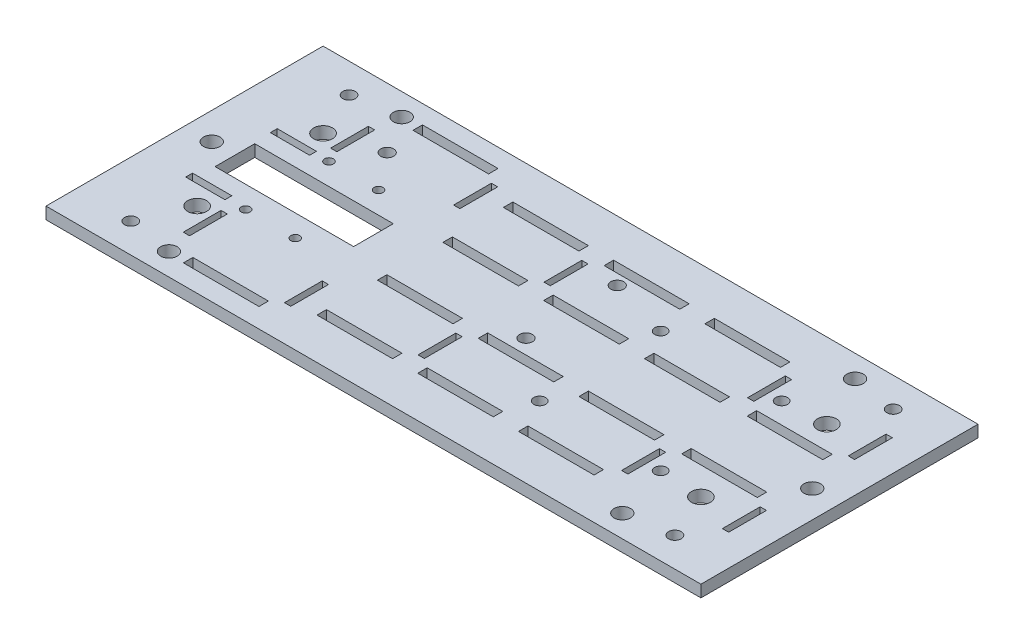
SolidWorks part; units mm, degrees
material "Thornel VCB-20 Carbon Cloth"
ref_plane "Front Plane" through (0, 0, 0) normal (0, 0, 1) x (1, 0, 0)
ref_plane "Top Plane" through (0, 0, 0) normal (0, 1, 0) x (1, 0, 0)
ref_plane "Right Plane" through (0, 0, 0) normal (1, 0, 0) x (0, 0, -1)
sketch "Sketch1" plane through (0, 0, 0) normal (0, 1, 0) x (1, 0, 0)
  line L0 (82.55, -34.925) -> (82.55, 34.925)
  line L1 (82.55, -34.925) -> (-82.55, -34.925)
  line L2 (82.55, 34.925) -> (-82.55, 34.925)
  line L3 (-82.55, -34.925) -> (-82.55, 34.925)
  line L4 (82.55, -34.925) -> (-82.55, 34.925) construction
  line L5 (82.55, 34.925) -> (-82.55, -34.925) construction
  point P1 (0, 0)
  dimension "D1" = 165.1
  dimension "D2" = 69.85
extrude "Boss-Extrude1" add sketch "Sketch1" along normal blind 3
sketch "Sketch6" plane through (0, 0, 0) normal (0, -1, 0) x (1, 0, 0)
  line L0 (-82.55, -34.925) -> (-82.55, 34.925) construction
  line L1 (-69.85, 5) -> (-34.925, 5)
  line L2 (-69.85, 5) -> (-69.85, -5)
  line L3 (-69.85, -5) -> (-34.925, -5)
  line L4 (-34.925, 5) -> (-34.925, -5)
  line L5 (6.775, -19.756) -> (-51.225, -19.756) construction
  line L6 (6.775, -19.756) -> (6.775, 3.246) construction
  line L7 (6.775, 3.246) -> (-51.225, 3.246) construction
  line L8 (-51.225, -19.756) -> (-51.225, 3.246) construction
  line L9 (6.775, -19.756) -> (-51.225, 3.246) construction
  line L10 (6.775, 3.246) -> (-51.225, -19.756) construction
  circle A0 centre (22.225, 15.25) radius 1.5
  circle A1 centre (52.725, 15.25) radius 1.5
  circle A2 centre (22.225, -15.25) radius 1.5
  circle A3 centre (52.725, -15.25) radius 1.5
  circle A4 centre (-51.225, 3.246) radius 1.625
  circle A5 centre (6.775, 3.246) radius 1.625
  circle A6 centre (6.775, -19.756) radius 1.625
  circle A7 centre (-51.225, -19.756) radius 1.625
  point P8 (-34.925, 0)
  point P9 (0, 0)
  point P16 (34.8354, 15.25)
  point P18 (-22.225, -8.255)
  point P27 (-26.6476, 0)
  point P28 (-25.4, -11.677)
  point P29 (-31.75, -5.9882)
  dimension "D5" = 3
  dimension "D6" = 3
  dimension "D7" = 3
  dimension "D8" = 3
  dimension "D18" = 3.25
  dimension "D1" = 34.925
  dimension "D2" = 10
  dimension "D3" = 12.7
  dimension "D4" = 30.5
  dimension "D9" = 30.5
  dimension "D10" = 30.5
  dimension "D11" = 15.25
  dimension "D12" = 22.225
  dimension "D13" = 15.25
  dimension "D14" = 15.25
  dimension "D15" = 15.25
  dimension "D16" = 23.002
  dimension "D17" = 58
  dimension "D19" = 60.325
  dimension "D20" = 8.255
extrude "Cut-Extrude1" cut sketch "Sketch6" against normal up to next contours A4 | L4 L1 L2 L3 A4 | A6 | A2 | A3 | A1 | A0 | A7 | A5 region at (-52.4158, 0, -0.079) region at (22.225, 0, 15.25) region at (52.725, 0, 15.25) region at (22.225, 0, -15.25) region at (52.725, 0, -15.25) region at (-51.225, 0, 3.246) region at (6.775, 0, -19.756)
sketch "Sketch7" plane through (0, 3, 0) normal (0, 1, 0) x (1, 0, 0)
  line L0 (-82.55, 34.925) -> (-82.55, -34.925) construction
  line L1 (82.55, -34.925) -> (82.55, 34.925) construction
  line L2 (-82.55, -34.925) -> (82.55, -34.925) construction
  line L3 (82.55, 34.925) -> (-82.55, 34.925) construction
  circle A0 centre (-77.47, 29.845) radius 1.5
  circle A1 centre (-77.47, -29.845) radius 1.5
  circle A2 centre (77.47, -29.845) radius 1.5
  circle A3 centre (77.47, 29.845) radius 1.5
  dimension "D9" = 3
  dimension "D10" = 3
  dimension "D11" = 3
  dimension "D12" = 3
  dimension "D1" = 5.08
  dimension "D2" = 5.08
  dimension "D3" = 5.08
  dimension "D4" = 5.08
  dimension "D5" = 5.08
  dimension "D6" = 5.08
  dimension "D7" = 5.08
  dimension "D8" = 5.08
sketch "Sketch8" plane through (0, 3, 0) normal (0, 1, 0) x (1, 0, 0)
  line L0 (-82.55, -34.925) -> (82.55, -34.925) construction
  line L1 (-82.55, 34.925) -> (-82.55, -34.925) construction
  line L2 (82.55, -34.925) -> (82.55, 34.925) construction
  line L3 (82.55, 34.925) -> (-82.55, 34.925) construction
  circle A0 centre (-63.5, -15.875) radius 2.3813
  circle A1 centre (-63.5, 15.875) radius 2.3813
  circle A2 centre (63.5, 15.875) radius 2.3813
  circle A3 centre (63.5, -15.875) radius 2.3813
  dimension "D1" = 4.7625
  dimension "D4" = 4.7625
  dimension "D5" = 4.7625
  dimension "D6" = 4.7625
  dimension "D2" = 19.05
  dimension "D3" = 19.05
  dimension "D7" = 19.05
  dimension "D8" = 19.05
  dimension "D9" = 19.05
  dimension "D10" = 19.05
  dimension "D11" = 19.05
  dimension "D12" = 19.05
extrude "Cut-Extrude3" cut sketch "Sketch8" against normal up to next
sketch "Sketch9" plane through (0, 3, 0) normal (0, 1, 0) x (1, 0, 0)
  line L0 (-82.55, 34.925) -> (-82.55, -34.925) construction
  line L1 (82.55, -34.925) -> (82.55, 34.925) construction
  circle A0 centre (-75.692, 0) radius 2.0828
  circle A1 centre (75.692, 0) radius 2.0828
  dimension "D1" = 6.858
  dimension "D2" = 6.858
extrude "Cut-Extrude5" cut sketch "Sketch9" against normal blind 5.08
sketch "Sketch10" plane through (0, 3, 0) normal (0, 1, 0) x (1, 0, 0)
  line L0 (-82.55, -34.925) -> (82.55, -34.925) construction
  line L1 (82.55, 34.925) -> (-82.55, 34.925) construction
  circle A0 centre (0, -29.337) radius 2.0828
  circle A1 centre (0, 29.337) radius 2.0828
  circle A2 centre (57.15, -29.337) radius 2.0828
  circle A3 centre (57.15, 29.337) radius 2.0828
  circle A4 centre (-57.15, -29.337) radius 2.0828
  circle A5 centre (-57.15, 29.337) radius 2.0828
  dimension "D1" = 5.588
  dimension "D2" = 5.588
  dimension "D3" = 2
  dimension "D4" = 2
extrude "Cut-Extrude6" cut sketch "Sketch10" against normal blind 5.08 contours A5 | A2 | A3 | A4 region at (57.15, 3, 29.337) region at (57.15, 3, -29.337) region at (-57.15, 3, 29.337) region at (-57.15, 3, -29.337)
sketch "Sketch11" plane through (0, 3, 0) normal (0, 1, 0) x (1, 0, 0)
  line L1 (-44.1375, 10.5) -> (-56.6375, 10.5) construction
  line L2 (-44.1375, 10.5) -> (-44.1375, -10.5) construction
  line L3 (-44.1375, -10.5) -> (-56.6375, -10.5) construction
  line L4 (-56.6375, 10.5) -> (-56.6375, -10.5) construction
  line L5 (-44.1375, 10.5) -> (-56.6375, -10.5) construction
  line L6 (-44.1375, -10.5) -> (-56.6375, 10.5) construction
  line L7 (-34.925, 5) -> (-69.85, 5) construction
  circle A0 centre (-56.6375, 10.5) radius 1.125
  circle A1 centre (-44.1375, 10.5) radius 1.125
  circle A2 centre (-44.1375, -10.5) radius 1.125
  circle A3 centre (-56.6375, -10.5) radius 1.125
  point P0 (-50.3875, 0)
  point P9 (-52.3875, 5)
  dimension "D4" = 2.25
  dimension "D5" = 2.25
  dimension "D6" = 2.25
  dimension "D7" = 2.25
  dimension "D1" = 12.5
  dimension "D2" = 21
  dimension "D3" = 2
extrude "Cut-Extrude7" cut sketch "Sketch11" against normal blind 41.91
sketch "Sketch12" plane through (0, 0, 0) normal (0, -1, 0) x (1, 0, 0)
  line L0 (-24.5963, 23.3735) -> (-5.5463, 23.3735) construction
  line L1 (-24.5963, 24.5641) -> (-5.5463, 24.5641)
  line L2 (-24.5963, 24.5641) -> (-24.5963, 22.1829)
  line L3 (-24.5963, 22.1829) -> (-5.5463, 22.1829)
  line L4 (-5.5463, 24.5641) -> (-5.5463, 22.1829)
  line L5 (-15.0713, 24.5641) -> (-15.0713, 22.1829)
  line L6 (0.8037, 24.5641) -> (0.8037, 22.1829)
  line L7 (0.8037, 24.5641) -> (19.8537, 24.5641)
  line L8 (19.8537, 24.5641) -> (19.8537, 22.1829)
  line L9 (0.8037, 22.1829) -> (19.8537, 22.1829)
  line L10 (26.2037, 24.5641) -> (26.2037, 22.1829)
  line L11 (26.2037, 24.5641) -> (45.2537, 24.5641)
  line L12 (45.2537, 24.5641) -> (45.2537, 22.1829)
  line L13 (26.2037, 22.1829) -> (45.2537, 22.1829)
  line L14 (0.8037, 9.3241) -> (0.8037, 6.9429)
  line L15 (0.8037, 9.3241) -> (19.8537, 9.3241)
  line L16 (19.8537, 9.3241) -> (19.8537, 6.9429)
  line L17 (0.8037, 6.9429) -> (19.8537, 6.9429)
  line L18 (26.2037, 9.3241) -> (26.2037, 6.9429)
  line L19 (26.2037, 9.3241) -> (45.2537, 9.3241)
  line L20 (45.2537, 9.3241) -> (45.2537, 6.9429)
  line L21 (26.2037, 6.9429) -> (45.2537, 6.9429)
  line L22 (-24.5963, 9.3241) -> (-24.5963, 6.9429)
  line L23 (-24.5963, 9.3241) -> (-5.5463, 9.3241)
  line L24 (-5.5463, 9.3241) -> (-5.5463, 6.9429)
  line L25 (-24.5963, 6.9429) -> (-5.5463, 6.9429)
  line L26 (-24.5963, 24.5641) -> (0.8037, 24.5641) construction
  line L27 (-71.2714, 9.2531) -> (-61.3765, 9.2531)
  line L28 (-24.5963, -24.8071) -> (0.8037, -24.8071) construction
  line L29 (-24.5963, -23.6165) -> (-5.5463, -23.6165) construction
  line L30 (-24.5963, -7.1859) -> (-5.5463, -7.1859)
  line L31 (-5.5463, -9.5671) -> (-5.5463, -7.1859)
  line L32 (-24.5963, -9.5671) -> (-5.5463, -9.5671)
  line L33 (-24.5963, -9.5671) -> (-24.5963, -7.1859)
  line L34 (26.2037, -7.1859) -> (45.2537, -7.1859)
  line L35 (45.2537, -9.5671) -> (45.2537, -7.1859)
  line L36 (26.2037, -9.5671) -> (45.2537, -9.5671)
  line L37 (26.2037, -9.5671) -> (26.2037, -7.1859)
  line L38 (0.8037, -7.1859) -> (19.8537, -7.1859)
  line L39 (19.8537, -9.5671) -> (19.8537, -7.1859)
  line L40 (0.8037, -9.5671) -> (19.8537, -9.5671)
  line L41 (0.8037, -9.5671) -> (0.8037, -7.1859)
  line L42 (26.2037, -22.4259) -> (45.2537, -22.4259)
  line L43 (45.2537, -24.8071) -> (45.2537, -22.4259)
  line L44 (26.2037, -24.8071) -> (45.2537, -24.8071)
  line L45 (26.2037, -24.8071) -> (26.2037, -22.4259)
  line L46 (0.8037, -22.4259) -> (19.8537, -22.4259)
  line L47 (19.8537, -24.8071) -> (19.8537, -22.4259)
  line L48 (0.8037, -24.8071) -> (19.8537, -24.8071)
  line L49 (0.8037, -24.8071) -> (0.8037, -22.4259)
  line L50 (-15.0713, -24.8071) -> (-15.0713, -22.4259)
  line L51 (-5.5463, -24.8071) -> (-5.5463, -22.4259)
  line L52 (-24.5963, -22.4259) -> (-5.5463, -22.4259)
  line L53 (-24.5963, -24.8071) -> (-24.5963, -22.4259)
  line L54 (-24.5963, -24.8071) -> (-5.5463, -24.8071)
  line L56 (-3.1651, 10.991) -> (-1.5776, 10.991)
  line L57 (-3.1651, 10.991) -> (-3.1651, 20.516)
  line L58 (-3.1651, 20.516) -> (-1.5776, 20.516)
  line L59 (-1.5776, 10.991) -> (-1.5776, 20.516)
  line L60 (-3.1651, 10.991) -> (-1.5776, 20.516) construction
  line L61 (-3.1651, 20.516) -> (-1.5776, 10.991) construction
  line L66 (-3.1651, -20.759) -> (-1.5776, -20.759)
  line L67 (-1.5776, -11.234) -> (-1.5776, -20.759)
  line L68 (-3.1651, -11.234) -> (-1.5776, -11.234)
  line L69 (-3.1651, -11.234) -> (-3.1651, -20.759)
  line L78 (51.6896, 8.9006) -> (51.6896, 6.5194)
  line L79 (51.6896, 8.9006) -> (70.7396, 8.9006)
  line L80 (70.7396, 8.9006) -> (70.7396, 6.5194)
  line L81 (51.6896, 6.5194) -> (70.7396, 6.5194)
  line L82 (-70.3121, -11.1231) -> (-60.4172, -11.1231)
  line L83 (64.3896, -0.545) -> (-18.1604, -0.545) construction
  line L84 (-70.3121, -11.1231) -> (-70.3121, -9.3903)
  line L85 (51.6896, -7.6094) -> (70.7396, -7.6094)
  line L86 (70.7396, -9.9906) -> (70.7396, -7.6094)
  line L87 (51.6896, -9.9906) -> (70.7396, -9.9906)
  line L88 (51.6896, -9.9906) -> (51.6896, -7.6094)
  line L93 (73.1208, 10.5675) -> (73.1208, 20.0925)
  line L94 (47.7208, 10.5675) -> (49.3083, 10.5675)
  line L95 (47.7208, 10.5675) -> (47.7208, 20.0925)
  line L96 (47.7208, 20.0925) -> (49.3083, 20.0925)
  line L97 (49.3083, 10.5675) -> (49.3083, 20.0925)
  line L98 (47.7208, 10.5675) -> (49.3083, 20.0925) construction
  line L99 (47.7208, 20.0925) -> (49.3083, 10.5675) construction
  line L100 (73.1208, 10.5675) -> (74.7083, 10.5675)
  line L101 (74.7083, 10.5675) -> (74.7083, 20.0925)
  line L102 (73.1208, 20.0925) -> (74.7083, 20.0925)
  line L103 (47.7208, 10.5675) -> (73.1208, 10.5675) construction
  line L104 (47.7208, -21.1825) -> (49.3083, -21.1825)
  line L105 (49.3083, -11.6575) -> (49.3083, -21.1825)
  line L106 (47.7208, -11.6575) -> (49.3083, -11.6575)
  line L107 (47.7208, -11.6575) -> (47.7208, -21.1825)
  line L108 (73.1208, -11.6575) -> (74.7083, -11.6575)
  line L109 (74.7083, -11.6575) -> (74.7083, -21.1825)
  line L110 (73.1208, -21.1825) -> (74.7083, -21.1825)
  line L111 (73.1208, -11.6575) -> (73.1208, -21.1825)
  line L112 (-70.3121, -9.3903) -> (-60.4172, -9.3903)
  line L113 (-60.4172, -11.1231) -> (-60.4172, -9.3903)
  line L114 (-52.8291, -27.8715) -> (-33.7791, -27.8715)
  line L115 (-33.7791, -30.2527) -> (-33.7791, -27.8715)
  line L116 (-52.8291, -30.2527) -> (-33.7791, -30.2527)
  line L117 (-52.8291, -30.2527) -> (-52.8291, -27.8715)
  line L118 (-70.3121, -11.1231) -> (-60.4172, -9.3903) construction
  line L123 (-59.3265, -23.1262) -> (-57.739, -23.1262)
  line L124 (-57.739, -13.6012) -> (-57.739, -23.1262)
  line L125 (-59.3265, -13.6012) -> (-57.739, -13.6012)
  line L126 (-59.3265, -13.6012) -> (-59.3265, -23.1262)
  line L127 (-31.3979, -16.6796) -> (-29.8104, -16.6796)
  line L128 (-29.8104, -16.6796) -> (-29.8104, -26.2046)
  line L129 (-31.3979, -26.2046) -> (-29.8104, -26.2046)
  line L130 (-31.3979, -16.6796) -> (-31.3979, -26.2046)
  line L131 (-70.3121, -9.3903) -> (-60.4172, -11.1231) construction
  line L132 (-71.2714, 9.2531) -> (-71.2714, 10.9859)
  line L133 (-31.3979, 16.4366) -> (-31.3979, 25.9616)
  line L134 (-31.3979, 25.9616) -> (-29.8104, 25.9616)
  line L135 (-29.8104, 16.4366) -> (-29.8104, 25.9616)
  line L136 (-31.3979, 16.4366) -> (-29.8104, 16.4366)
  line L137 (-59.5464, 13.798) -> (-59.5464, 23.323)
  line L138 (-59.5464, 13.798) -> (-57.9589, 13.798)
  line L139 (-57.9589, 13.798) -> (-57.9589, 23.323)
  line L140 (-59.5464, 23.323) -> (-57.9589, 23.323)
  line L145 (-71.2714, 10.9859) -> (-61.3765, 10.9859)
  line L146 (-52.8291, 30.0097) -> (-52.8291, 27.6285)
  line L147 (-52.8291, 30.0097) -> (-33.7791, 30.0097)
  line L148 (-33.7791, 30.0097) -> (-33.7791, 27.6285)
  line L149 (-52.8291, 27.6285) -> (-33.7791, 27.6285)
  line L150 (-61.3765, 9.2531) -> (-61.3765, 10.9859)
  point P8 (-65.3646, -10.2567)
  point P60 (-2.3713, 15.7535)
  point P100 (48.5146, 15.33)
  dimension "D1" = 19.05
  dimension "D2" = 2.3813
  dimension "D3" = 25.4
  dimension "D4" = 15.24
  dimension "D5" = 1.5875
  dimension "D6" = 3.175
  dimension "D7" = 9.525
  dimension "D8" = 7.62
extrude "Cut-Extrude8" cut sketch "Sketch12" against normal blind 21.336 contours L37 L36 L35 L34 | L88 L87 L86 L85 | L45 L44 L43 L42 | L117 L116 L115 L114 | L78 L81 L80 L79 | L10 L13 L12 L11 | L6 L9 L8 L7 | L14 L17 L16 L15 | L107 L104 L105 L106 | L109 L110 L111 L108 | L40 L39 L38 L41 | L48 L47 L46 L49 | L67 L66 L69 L68 | L52 L51 L54 L53 | L30 L31 L32 L33 | L130 L129 L128 L127 | L126 L123 L124 L125 | L93 L102 L101 L100 | L97 L96 L95 L94 | L19 L20 L21 L18 | L56 L59 L58 L57 | L25 L24 L23 L22 | L3 L4 L1 L2 | L135 L134 L133 L136 | L149 L148 L147 L146 | L139 L140 L137 L138 | L27 L150 L145 L132 | L84 L82 L113 L112 region at (10.3287, 0, 23.3735) region at (35.7287, 0, 23.3735) region at (10.3287, 0, 8.1335) region at (35.7287, 0, -8.3765) region at (35.7287, 0, -23.6165) region at (61.2146, 0, 7.71) region at (61.2146, 0, -8.8) region at (-43.3041, 0, -29.0621)
sketch "Sketch13" plane through (0, 0, 0) normal (0, -1, 0) x (1, 0, 0)
  line L0 (0, 18.4306) -> (0, -15.755) construction
  circle A0 centre (-68.5804, 27.5146) radius 1.5875 construction
  circle A1 centre (-68.5804, -27.5146) radius 1.5875 construction
  circle A2 centre (-68.5804, 27.5146) radius 1.5875
  circle A3 centre (-68.5804, -27.5146) radius 1.5875
  circle A4 centre (68.5804, -27.5146) radius 1.5875
  circle A5 centre (68.5804, 27.5146) radius 1.5875
extrude "Cut-Extrude10" cut sketch "Sketch13" against normal blind 28.034
